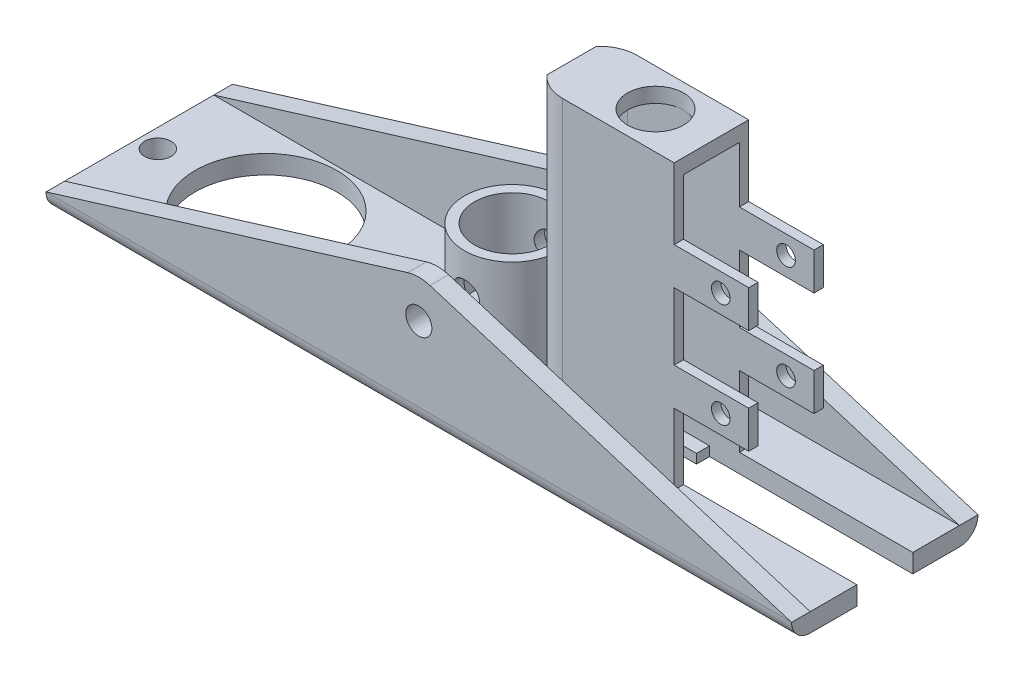
SolidWorks part; units mm, degrees
material "AISI 1035 Steel (SS)"
ref_plane "Front Plane" through (0, 0, 0) normal (0, 0, 1) x (1, 0, 0)
ref_plane "Top Plane" through (0, 0, 0) normal (0, 1, 0) x (1, 0, 0)
ref_plane "Right Plane" through (0, 0, 0) normal (1, 0, 0) x (0, 0, -1)
sketch "Sketch2" plane through (0, 0, 0) normal (0, 1, 0) x (1, 0, 0)
  line L0 (-100, -25) -> (100, -25)
  line L1 (100, -25) -> (100, 25)
  line L2 (100, 25) -> (-100, 25)
  line L3 (-100, 25) -> (-100, -25)
  line L4 (-66, 25) -> (-66, -25) construction
  line L5 (0, -55) -> (0, 55) construction
  circle A1 centre (-66, 0) radius 19
  circle A2 centre (-37, 0) radius 3.55
  circle A3 centre (-95, 0) radius 3.55
  point P6 (-100, 0)
  point P12 (0, 25)
  dimension "D4" = 38
  dimension "D5" = 7.1
  dimension "D1" = 200
  dimension "D2" = 50
  dimension "D6" = 29
  dimension "D3" = 5
  dimension "D7" = 66
extrude "Boss-Extrude1" add sketch "Sketch2" along normal blind 5
sketch "Sketch6" plane through (0, 0, 0) normal (0, 0, 1) x (1, 0, 0)
  line L0 (-100, 5) -> (-2.9907, 34.7517)
  line L1 (2.9907, 34.7517) -> (100, 5)
  line L2 (100, 5) -> (100, 0) construction
  line L3 (-100, 5) -> (100, 5)
  line L4 (-100, 5) -> (-100, 0) construction
  line L5 (27.5, 0) -> (-27.5, 0) construction
  arc A0 (2.9907, 34.7517) -> (-2.9907, 34.7517) centre (0, 25) ccw
  point P11 (0, 5)
  dimension "D1" = 20.4
  dimension "D2" = 20
  dimension "D4" = 5
extrude "Boss-Extrude3" add sketch "Sketch6" against normal up to surface and the other way up to surface up to face at (0, 2.5, -25) other way up to face at (0, 2.5, 25)
sketch "Sketch7" plane through (0, 0, 0) normal (0, 0, 1) x (1, 0, 0)
  line L0 (2.9907, 34.7517) -> (100, 5) construction
  line L1 (-100, 5) -> (-2.9907, 34.7517) construction
  line L2 (2.9907, 34.7517) -> (100, 5)
  line L3 (-100, 5) -> (-2.9907, 34.7517)
  line L4 (-100, 5) -> (100, 5)
  arc A0 (2.9907, 34.7517) -> (-2.9907, 34.7517) centre (0, 25) ccw construction
  arc A1 (2.9907, 34.7517) -> (-2.9907, 34.7517) centre (0, 25) ccw
extrude "Cut-Extrude2" cut sketch "Sketch7" against normal offset from surface 5 and the other way offset from surface 5 contours L2 A1 L3 L4 region at (0, 15.2168, 0) up to face at (0, 13.3253, -25) other way up to face at (0, 13.3253, 25)
sketch "Sketch22" [suppressed] plane through (0, 0, 0) normal (0, 0, 1) x (1, 0, 0)
  line L10 (-25.5, 27.8483) -> (-25.5, 5)
  line L11 (0, -19.36) -> (0, 19.36) construction
  line L13 (-100, 5) -> (-25.5, 5)
  line L14 (-100, 5) -> (-2.9907, 34.7517) construction
  line L15 (-25.5, 27.8483) -> (-100, 5)
  dimension "D1" = 25.5
extrude "Cut-Extrude9" [suppressed] cut sketch "Sketch22" against normal offset from surface 5 and the other way offset from surface 5 up to face at (0, 13.3253, -25) other way up to face at (0, 13.3253, 25)
sketch "Sketch8" plane through (0, 5, 0) normal (0, 1, 0) x (1, 0, 0)
  circle A0 centre (0, 0) radius 10.05
  circle A1 centre (0, 0) radius 12.75
  dimension "D1" = 20.1
  dimension "D2" = 25.5
extrude "Boss-Extrude4" add sketch "Sketch8" along normal blind 30.2
fillet "Fillet1" radius 5 2 edges at (0, 0, -25) (0, 0, 25)
sketch "Sketch9" plane through (0, 0, 25) normal (0, 0, 1) x (1, 0, 0)
  line L0 (0, -19.36) -> (0, 19.36) construction
  line L1 (-100, 5) -> (100, 5) construction
  circle A0 centre (0, 25) radius 3.5
  dimension "D2" = 20
  dimension "D1" = 7
extrude "Cut-Extrude3" cut sketch "Sketch9" against normal through all
sketch "Sketch13" plane through (0, 5, 0) normal (0, 1, 0) x (1, 0, 0)
  line L0 (23.5, 0) -> (53.5, 0) construction
  line L1 (23.5, 7.5) -> (53.5, 7.5)
  line L2 (23.5, -7.5) -> (53.5, -7.5)
  arc A0 (23.5, 7.5) -> (23.5, -7.5) centre (23.5, 0) ccw
  arc A1 (53.5, -7.5) -> (53.5, 7.5) centre (53.5, 0) ccw
  circle A2 centre (31.5, 0) radius 2
  circle A4 centre (24.5, 0) radius 2
  circle A5 centre (38.5, 0) radius 2
  circle A6 centre (45.5, 0) radius 2
  circle A7 centre (52.5, 0) radius 2
  point P3 (38.5, 0)
  point P8 (16, 0)
  point P24 (38.5, 7.5)
  dimension "D3" = 16
  dimension "D4" = 4
  dimension "D1" = 30
  dimension "D2" = 7.5
  dimension "D6" = 7
  dimension "D5" = 5
extrude "Cut-Extrude5" cut sketch "Sketch13" against normal blind 2.5
sketch "Sketch15" plane through (0, 5, 0) normal (0, 1, 0) x (1, 0, 0)
  line L0 (23.5, 0) -> (53.5, 0) construction
  line L1 (23.5, 4) -> (53.5, 4)
  line L2 (23.5, -4) -> (53.5, -4)
  line L3 (53.5, 7.5) -> (23.5, 7.5) construction
  line L4 (53.5, 4) -> (100, 4)
  line L5 (100, 20) -> (100, -20) construction
  line L6 (100, 4) -> (100, -4)
  line L7 (100, -4) -> (53.5, -4)
  arc A5 (23.5, 4) -> (23.5, -4) centre (23.5, 0) ccw
  point P3 (38.5, 0)
  point P6 (100, 0)
  point P14 (38.5, 4)
  point P23 (38.5, 7.5)
  dimension "D1" = 30
  dimension "D3" = 4
  dimension "D2" = 8
extrude "Cut-Extrude6" cut sketch "Sketch15" against normal through all
sketch "Sketch16" plane through (0, 5, 0) normal (0, 1, 0) x (1, 0, 0)
  line L0 (16, -4) -> (16, -6.6144)
  line L9 (53.5, 7.5) -> (23.5, 7.5) construction
  line L10 (59.8443, 4) -> (23.5, 4) construction
  line L11 (23.5, -4) -> (59.8443, -4) construction
  line L15 (23.5, -7.5) -> (53.5, -7.5) construction
  line L16 (23.5, -7.5) -> (53.5, -7.5)
  line L17 (23.5, -10) -> (53.5, -10)
  line L18 (53.5, 10) -> (23.5, 10)
  line L19 (23.5, -10) -> (53.5, -10)
  line L20 (53.5, 10) -> (23.5, 10)
  line L21 (53.5, 7.5) -> (23.5, 7.5)
  line L22 (53.5, 10) -> (53.5, 7.5)
  line L23 (53.5, -7.5) -> (53.5, -10)
  line L24 (16, 6.6144) -> (16, 4)
  line L25 (17.1557, 4) -> (16, 4)
  line L26 (17.1557, -4) -> (16, -4)
  arc A0 (17.1557, -4) -> (23.5, -7.5) centre (23.5, 0) ccw
  arc A1 (23.5, 7.5) -> (23.5, -7.5) centre (23.5, 0) ccw construction
  arc A2 (23.5, 10) -> (23.5, -10) centre (23.5, 0) ccw
  arc A3 (23.5, 10) -> (16, 6.6144) centre (23.5, 0) ccw
  arc A4 (23.5, 7.5) -> (17.1557, 4) centre (23.5, 0) ccw
  arc A5 (16, -6.6144) -> (23.5, -10) centre (23.5, 0) ccw
  point P10 (16, 0)
  dimension "D1" = 2.5
extrude "Boss-Extrude7" add sketch "Sketch16" along normal blind 72
sketch "Sketch17" plane through (0, 77, 0) normal (0, 1, 0) x (1, 0, 0)
  line L0 (23.5, -10) -> (53.5, -10) construction
  line L1 (53.5, 10) -> (23.5, 10) construction
  line L2 (23.5, -10) -> (53.5, -10)
  line L3 (53.5, 10) -> (23.5, 10)
  line L4 (16, -4) -> (16, -6.6144) construction
  line L6 (16, 6.6144) -> (16, 4) construction
  line L8 (16, -4) -> (16, -6.6144)
  line L10 (16, 6.6144) -> (16, 4)
  line L12 (16, 4) -> (16, -4)
  line L13 (53.5, 10) -> (53.5, -10)
  arc A2 (53.5, 10) -> (53.5, -10) centre (53.5, 0) cw construction
  circle A3 centre (38.5, 0) radius 7.5
  arc A4 (16, -6.6144) -> (23.5, -10) centre (23.5, 0) ccw construction
  arc A5 (23.5, 10) -> (16, 6.6144) centre (23.5, 0) ccw construction
  arc A6 (16, -6.6144) -> (23.5, -10) centre (23.5, 0) ccw
  arc A7 (23.5, 10) -> (16, 6.6144) centre (23.5, 0) ccw
  point P9 (38.5, 10)
  dimension "D1" = 15
extrude "Boss-Extrude8" add sketch "Sketch17" along normal blind 4
sketch "Sketch18" plane through (0, 5, 0) normal (0, 1, 0) x (1, 0, 0)
  circle A0 centre (0, 0) radius 10.05
  circle A1 centre (0, 0) radius 10.05 construction
extrude "Boss-Extrude9" add sketch "Sketch18" along normal blind 9.5
sketch "Sketch19" plane through (53.5, 0, 0) normal (1, 0, 0) x (0, 0, -1)
  line L0 (-10, 81) -> (-10, 5) construction
  line L1 (-10, 62) -> (-7.5, 62)
  line L2 (-10, 62) -> (-10, 52)
  line L3 (-10, 52) -> (-7.5, 52)
  line L4 (-7.5, 62) -> (-7.5, 52)
  line L5 (-7.5, 77) -> (-7.5, 5) construction
  line L6 (7.5, 77) -> (7.5, 5) construction
  line L7 (7.5, 62) -> (10, 62)
  line L8 (7.5, 62) -> (7.5, 52)
  line L9 (7.5, 52) -> (10, 52)
  line L10 (10, 62) -> (10, 52)
  line L11 (10, 81) -> (10, 5) construction
  line L12 (7.5, 77) -> (-7.5, 77) construction
  line L13 (-10, 43) -> (10, 43) construction
  line L14 (-10, 81) -> (-10, 5) construction
  line L15 (10, 81) -> (10, 5) construction
  line L16 (7.5, 34) -> (10, 34)
  line L17 (10, 24) -> (10, 34)
  line L18 (7.5, 24) -> (10, 24)
  line L19 (7.5, 24) -> (7.5, 34)
  line L20 (-10, 34) -> (-7.5, 34)
  line L21 (-7.5, 24) -> (-7.5, 34)
  line L22 (-10, 24) -> (-7.5, 24)
  line L23 (-10, 24) -> (-10, 34)
  dimension "D1" = 10
  dimension "D2" = 15
extrude "Boss-Extrude10" add sketch "Sketch19" along normal blind 20
sketch "Sketch20" plane through (0, 0, 10) normal (0, 0, 1) x (1, 0, 0)
  line L0 (53.5, 43) -> (73.5, 43) construction
  line L1 (53.5, 52) -> (53.5, 34) construction
  line L2 (73.5, 62) -> (73.5, 52) construction
  line L3 (53.5, 52) -> (53.5, 34) construction
  circle A0 centre (66, 57) radius 2.5
  circle A1 centre (66, 29) radius 2.5
  point P6 (73.5, 57)
  dimension "D1" = 5
  dimension "D2" = 12.5
extrude "Cut-Extrude7" cut sketch "Sketch20" against normal through all
sketch "Sketch21" plane through (100, 0, 0) normal (1, 0, 0) x (0, 0, -1)
  line L0 (-20, 0) -> (-4, 0) construction
  line L1 (-4, 5) -> (-7.5, 5)
  line L2 (-4, 5) -> (-4, 0)
  line L3 (-4, 0) -> (-7.5, 0)
  line L4 (-7.5, 5) -> (-7.5, 0)
  line L6 (4, 5) -> (7.5, 5)
  line L7 (4, 5) -> (4, 0)
  line L8 (4, 0) -> (7.5, 0)
  line L9 (7.5, 5) -> (7.5, 0)
  line L10 (7.5, 2.5) -> (7.5, 77) construction
  line L11 (-7.5, 2.5) -> (-7.5, 77) construction
  line L12 (4, 0) -> (20, 0) construction
extrude "Cut-Extrude8" cut sketch "Sketch21" against normal offset from surface (54.5 mm away) 8 up to face at (53.5, 14.5, 8.75) offset beyond the face yes
sketch "Sketch23" [suppressed] plane through (0, 5, 0) normal (0, 1, 0) x (1, 0, 0)
  circle A0 centre (0, 0) radius 10.55
  dimension "D1" = 21.1
extrude "Cut-Extrude10" [suppressed] cut sketch "Sketch23" along normal through all
equation "\"H\"=20"
equation "\"D2@Sketch6\"=\"H\""
equation "\"Height\"= \"H\" + 10.2"
equation "\"D2@Sketch9\"=\"H\""
equation "\"D1@Boss-Extrude4\"=\"Height\""
equation "\"Length\"=200"
equation "\"D1@Sketch2\"=\"Length\""
equation "\"Width\"=50"
equation "\"D2@Sketch2\"=\"Width\""
equation "\"CylWidth\"=20.1"
equation "\"D1@Sketch8\"=\"CylWidth\""
equation "\"D2@Sketch8\"   = \"CylWidth\"+10"
equation "\"HoleWidth\"=38"
equation "\"D4@Sketch2\"=\"HoleWidth\""
equation "\"HoleDist\"= 35"
